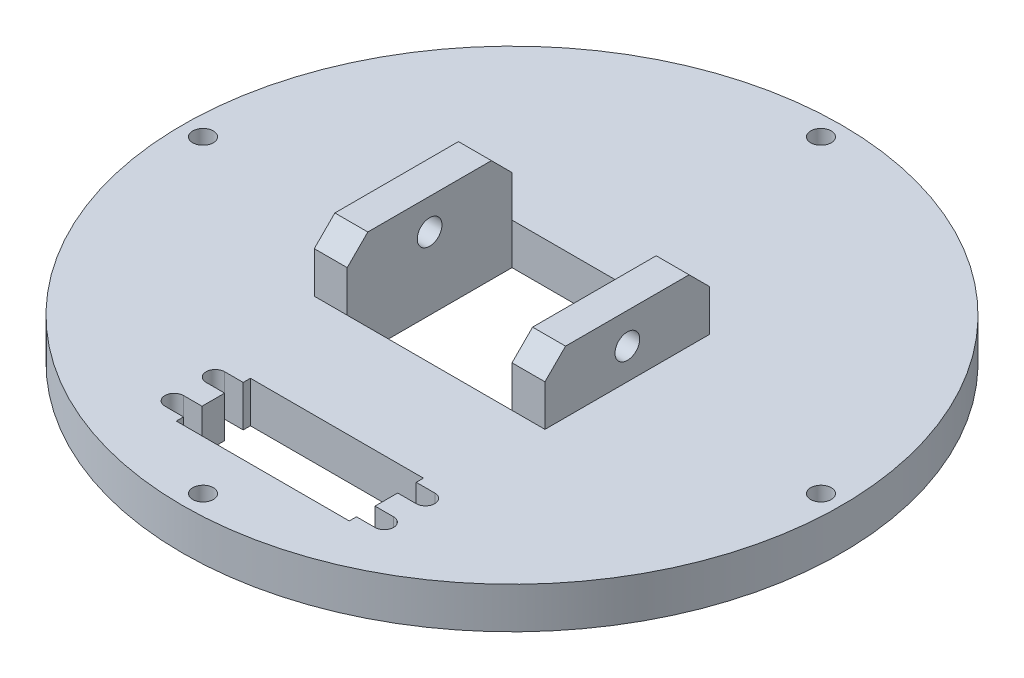
SolidWorks part; units mm, degrees
ref_plane "Front Plane" through (0, 0, 0) normal (0, 0, 1) x (1, 0, 0)
ref_plane "Top Plane" through (0, 0, 0) normal (0, 1, 0) x (1, 0, 0)
ref_plane "Right Plane" through (0, 0, 0) normal (1, 0, 0) x (0, 0, -1)
sketch "Sketch1" plane through (0, 0, 0) normal (0, 1, 0) x (1, 0, 0)
  circle A0 centre (0, 0) radius 80
  point P0 (0, 0)
  dimension "D1" = 160
extrude "Boss-Extrude1" add sketch "Sketch1" along normal blind 10 contours A0
sketch "Sketch2" plane through (0, 10, 0) normal (0, 1, 0) x (1, 0, 0)
  circle A0 centre (0, 0) radius 75 construction
  circle A1 centre (-75, 0) radius 2.5
  circle A2 centre (0, 75) radius 2.5
  circle A3 centre (75, 0) radius 2.5
  circle A4 centre (0, -75) radius 2.5
  point P3 (0, 75)
  point P4 (75, 0)
  point P5 (0, -75)
  point P6 (-75, 0)
  point P7 (-75, 0)
  point P12 (0, 75)
  point P15 (75, 0)
  point P18 (1.0208, -74.9931)
  point P19 (0, -75)
  dimension "D1" = 150
extrude "Cut-Extrude1" cut sketch "Sketch2" against normal up to next
sketch "Sketch3" plane through (0, 10, 0) normal (0, 1, 0) x (1, 0, 0)
  line L1 (-20, 20) -> (20, 20)
  line L2 (-20, 20) -> (-20, -20)
  line L3 (-20, -20) -> (20, -20)
  line L4 (20, 20) -> (20, -20)
  dimension "D1" = 40
  dimension "D2" = 20
  dimension "D3" = 20
extrude "Cut-Extrude2" cut sketch "Sketch3" against normal up to next
sketch "Sketch4" plane through (0, 10, 0) normal (0, 1, 0) x (1, 0, 0)
  line L0 (20, -20) -> (20, 20) construction
  line L1 (-18.5, -45) -> (23.5, -45)
  line L2 (-18.5, -45) -> (-18.5, -63)
  line L3 (-18.5, -63) -> (23.5, -63)
  line L4 (23.5, -45) -> (23.5, -63)
  line L5 (-20, -20) -> (20, -20) construction
  line L6 (-23, -59) -> (-18.5, -59) construction
  line L7 (-23, -49) -> (-23, -59)
  line L8 (-23, -49) -> (-18.5, -49) construction
  line L9 (-23, -46.75) -> (-18.5, -46.75)
  line L10 (-23, -51.25) -> (-18.5, -51.25)
  line L11 (28, -49) -> (28, -59)
  line L12 (-23, -56.75) -> (-18.5, -56.75)
  line L13 (-23, -61.25) -> (-18.5, -61.25)
  line L14 (23.5, -59) -> (28, -59) construction
  line L15 (23.5, -56.75) -> (28, -56.75)
  line L16 (23.5, -61.25) -> (28, -61.25)
  line L17 (23.5, -49) -> (28, -49) construction
  line L18 (23.5, -46.75) -> (28, -46.75)
  line L19 (23.5, -51.25) -> (28, -51.25)
  arc A2 (-23, -46.75) -> (-23, -51.25) centre (-23, -49) ccw
  arc A3 (-18.5, -51.25) -> (-18.5, -46.75) centre (-18.5, -49) ccw
  arc A4 (-23, -56.75) -> (-23, -61.25) centre (-23, -59) ccw
  arc A5 (-18.5, -61.25) -> (-18.5, -56.75) centre (-18.5, -59) ccw
  arc A6 (23.5, -56.75) -> (23.5, -61.25) centre (23.5, -59) ccw
  arc A7 (28, -61.25) -> (28, -56.75) centre (28, -59) ccw
  arc A8 (23.5, -46.75) -> (23.5, -51.25) centre (23.5, -49) ccw
  arc A9 (28, -51.25) -> (28, -46.75) centre (28, -49) ccw
  point P9 (-20.75, -59)
  point P12 (-20.75, -49)
  point P24 (25.75, -59)
  point P30 (25.75, -49)
  dimension "D5" = 4.5
  dimension "D8" = 4.5
  dimension "D10" = 2.25
  dimension "D9" = 2.25
  dimension "D11" = 2.25
  dimension "D12" = 2.25
  dimension "D1" = 42
  dimension "D2" = 18
  dimension "D3" = 3.5
  dimension "D4" = 25
  dimension "D6" = 10
  dimension "D7" = 4
extrude "Cut-Extrude3" cut sketch "Sketch4" against normal up to next contours A8 L4 L1 L2 A3 A5 L3 A6 | L2 A3 | L9 A2 L10 L2 | A4 L13 L2 L12 | L4 A8 | A9 L18 L4 L19 | L16 A7 L15 L4 | L2 A5 | A6 L16 A7 L15 | L4 L3 L2 L1 region at (2.5, 10, 54) region at (-17.5451, 10, 49) region at (-21.6537, 10, 49) region at (26.6537, 10, 49) region at (22.5451, 10, 49) region at (-17.5451, 10, 59) region at (-21.6537, 10, 59) region at (26.6537, 10, 59)
sketch "Sketch5" plane through (0, 10, 0) normal (0, 1, 0) x (1, 0, 0)
  line L0 (-20, -20) -> (20, -20) construction
  line L1 (-20, 20) -> (-28, 20)
  line L2 (-20, 20) -> (-20, -20)
  line L3 (-20, -20) -> (-28, -20)
  line L4 (-28, 20) -> (-28, -20)
  dimension "D1" = 8
extrude "Boss-Extrude2" add sketch "Sketch5" along normal blind 15
fillet "Fillet1" radius 5 2 edges at (-24, 25, -20) (-24, 25, 20) profile chamfer
sketch "Sketch6" plane through (-28, 0, 0) normal (-1, 0, 0) x (0, 0, 1)
  line L0 (-15, 25) -> (15, 25) construction
  line L2 (20, 20) -> (20, 10) construction
  circle A0 centre (0, 17.5) radius 3
  point P2 (0, 0)
  point P5 (0, 0)
  dimension "D1" = 6
  dimension "D2" = 7.5
  dimension "D3" = 20
extrude "Cut-Extrude4" cut sketch "Sketch6" against normal up to next
ref_plane "Plane1" [suppressed] through (0, 0, 0) normal (-1, 0, 0) x (0, 0, 1)
mirror "Mirror1" about plane through (0, 0, 0) normal (-1, 0, 0) of "Cut-Extrude4", "Fillet1", "Boss-Extrude2"
